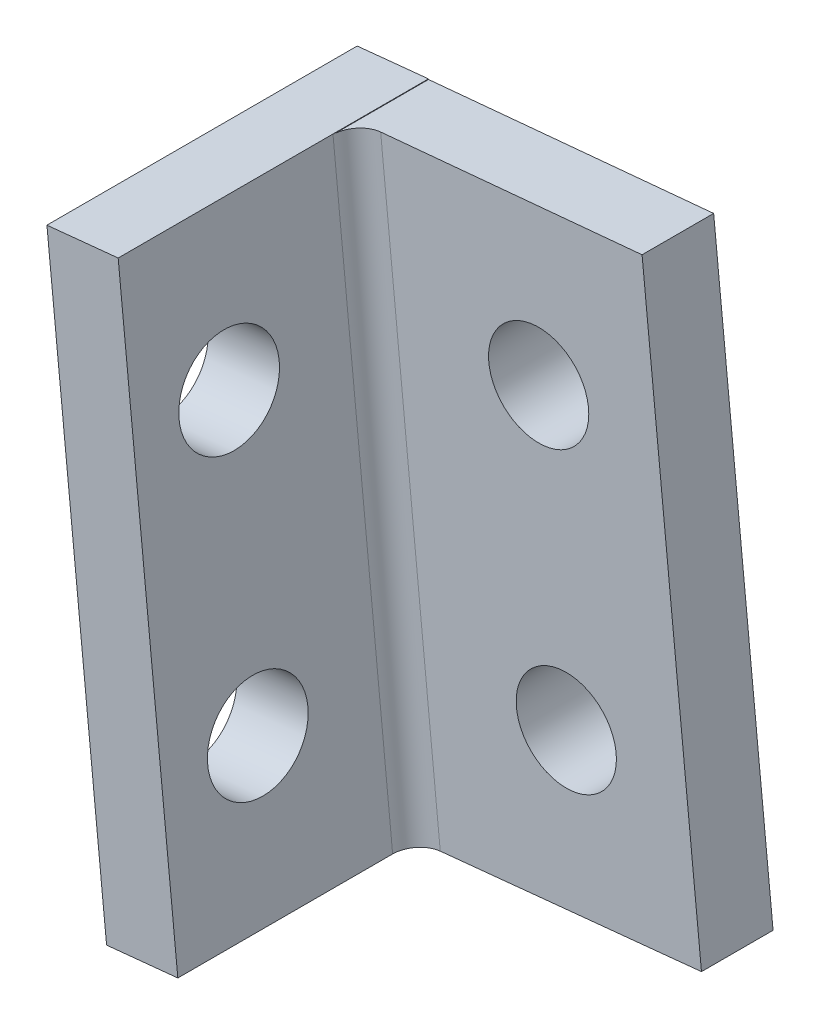
SolidWorks part; units mm, degrees
material "PLA"
ref_plane "Front Plane" through (0, 0, 0) normal (0, 0, 1) x (1, 0, 0)
ref_plane "Top Plane" through (0, 0, 0) normal (0, 1, 0) x (1, 0, 0)
ref_plane "Right Plane" through (0, 0, 0) normal (1, 0, 0) x (0, 0, -1)
sketch "Sketch1" plane through (0, 0, 0) normal (0, 0, 1) x (1, 0, 0)
  line L0 (-105, 44.7368) -> (-102.5, 19.8621)
  line L1 (-102.5, 19.8621) -> (-87.5752, 21.3621)
  line L2 (-87.5752, 21.3621) -> (-90.0649, 46.1302)
  line L3 (-90.0649, 46.1302) -> (-105, 44.7368)
  line L4 (-103.75, 32.2995) -> (-88.82, 33.7461) construction
  line L5 (-94.3968, 39.2339) -> (-93.2395, 27.2898) construction
  arc A0 (105, 44.7368) -> (-105, 44.7368) centre (0, -1000) ccw construction
  circle A2 centre (-94.3968, 39.2339) radius 2.1
  circle A3 centre (-93.2395, 27.2898) radius 2.1
  point P11 (0, 0)
  point P17 (-110.7999, 25.0506)
  point P18 (-94.3968, 39.2339)
  point P19 (-93.2395, 27.2898)
  dimension "D2" = 4.2
  dimension "D1" = 15
  dimension "D3" = 6
  dimension "D4" = 5
  dimension "D5" = 25
extrude "Boss-Extrude1" add sketch "Sketch1" along normal blind 3
sketch "Sketch3" plane through (-99.4987, -10, 0) normal (-0.995, -0.1, 0) x (0, 0, 1)
  line L0 (0, 55.0126) -> (0, 30.0126) construction
  line L1 (0, 30.0126) -> (13, 30.0126)
  line L2 (0, 30.0126) -> (0, 55.0126)
  line L3 (0, 55.0126) -> (13, 55.0126)
  line L4 (13, 30.0126) -> (13, 55.0126)
  line L5 (3, 30.0126) -> (0, 30.0126) construction
  line L6 (3, 55.0126) -> (0, 55.0126) construction
  line L7 (3, 55.0126) -> (3, 30.0126) construction
  line L8 (3, 42.5126) -> (13, 42.5126) construction
  circle A0 centre (9, 36.5126) radius 2.1
  circle A1 centre (9, 48.5126) radius 2.1
  dimension "D2" = 4.2
  dimension "D1" = 10
  dimension "6" = 6
  dimension "D4" = 6
extrude "Boss-Extrude2" add sketch "Sketch3" against normal blind 3
fillet "Fillet1" radius 1 1 edges at (-100.764, 32.5888, 3)
